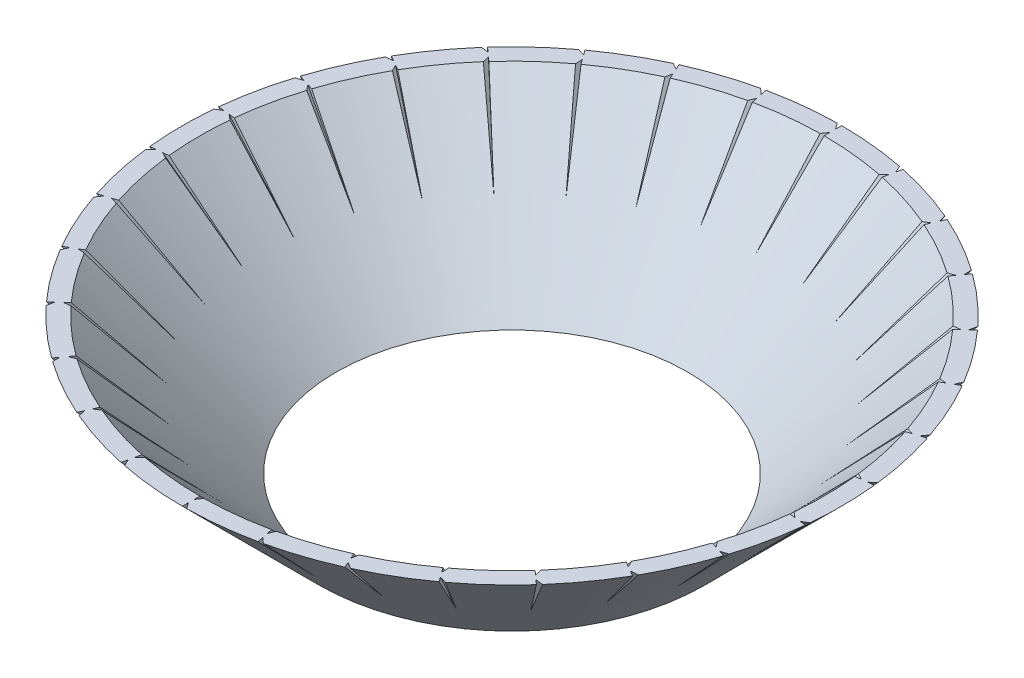
SolidWorks part; units mm, degrees
revolve "Base-Revolve" add sketch "Sketch1" angle 360 about L0
sketch "Sketch1" plane through (0, 0, 0) normal (1, 0, 0) x (0, 0, -1)
  line L0 (0, -30) -> (0, 30) construction
  line L1 (8.5, 0) -> (15.1, 6.6)
  line L2 (8.5, 0) -> (9.3485, 0)
  line L3 (9.3485, 0) -> (15.9485, 6.6)
  line L4 (15.1, 6.6) -> (15.9485, 6.6)
  dimension "D1" = 45
  dimension "InsideDia" = 17
  dimension "OutsideDia" = 30.2
  dimension "Thickness" = 0.6
ref_plane "Plane1" through (0, 0, 0) normal (0, 0, 1) x (1, 0, 0)
ref_plane "Plane2" through (0, 0, 0) normal (0, 1, 0) x (1, 0, 0)
ref_plane "Plane3" through (0, 0, 0) normal (1, 0, 0) x (0, 0, -1)
sketch "Sketch3" plane through (0, 0, 0) normal (1, 0, 0) x (0, 0, -1)
  line L1 (11.8, 3.3) -> (16.4649, 7.6)
  line L3 (8.5, 0) -> (15.1, 6.6) construction
  line L4 (15.9485, 6.6) -> (-15.9485, 6.6) construction
  point P4 (15.38, 6.6)
  dimension "D1" = 3.3
  dimension "D2" = 15.38
  dimension "D3" = 1
ref_plane "Plane4" through (0, 3.3, -11.8) normal (0, 0.6778, -0.7353) x (-1, 0, 0)
sketch "Sketch5" plane through (0, 3.3, -11.8) normal (0, 0.6778, -0.7353) x (-1, 0, 0)
  line L0 (0, 0) -> (0, 1)
  line L1 (0, 1) -> (1, 1)
  line L2 (1, 1) -> (0, 0)
  dimension "D1" = 1
  dimension "D2" = 1
sweep "Cut-Sweep1" cut profiles "Sketch5" path "Sketch3"
ref_plane "Plane6" through (0, 3.3, -12.6485) normal (0, -0.7071, -0.7071) x (1, 0, 0)
ref_plane "Plane7" through (0, -4.4621, -4.4621) normal (0, -0.7071, -0.7071) x (1, 0, 0)
mirror "Mirror2" about plane through (0, -4.4621, -4.4621) normal (0, -0.7071, -0.7071) of "Cut-Sweep1"
pattern_circular "CirPattern1" count 30 over 360 about axis through (0, -30, 0) along (0, 1, 0) of "Mirror2", "Cut-Sweep1"
equation "\"D1@Sketch3\" = ( \"OutsideDia@Sketch1\" - \"InsideDia@Sketch1\" )  / 4"
equation "\"D2@Sketch3\" = \"OutsideDia@Sketch1\" / 2 + (sqr(\"Thickness@Sketch1\" * \"Thickness@Sketch1\" + \"Thickness@Sketch1\" * \"Thickness@Sketch1\") * .33)"
equation "\"D1@Plane7\" = \"Thickness@Sketch1\" / 2"
